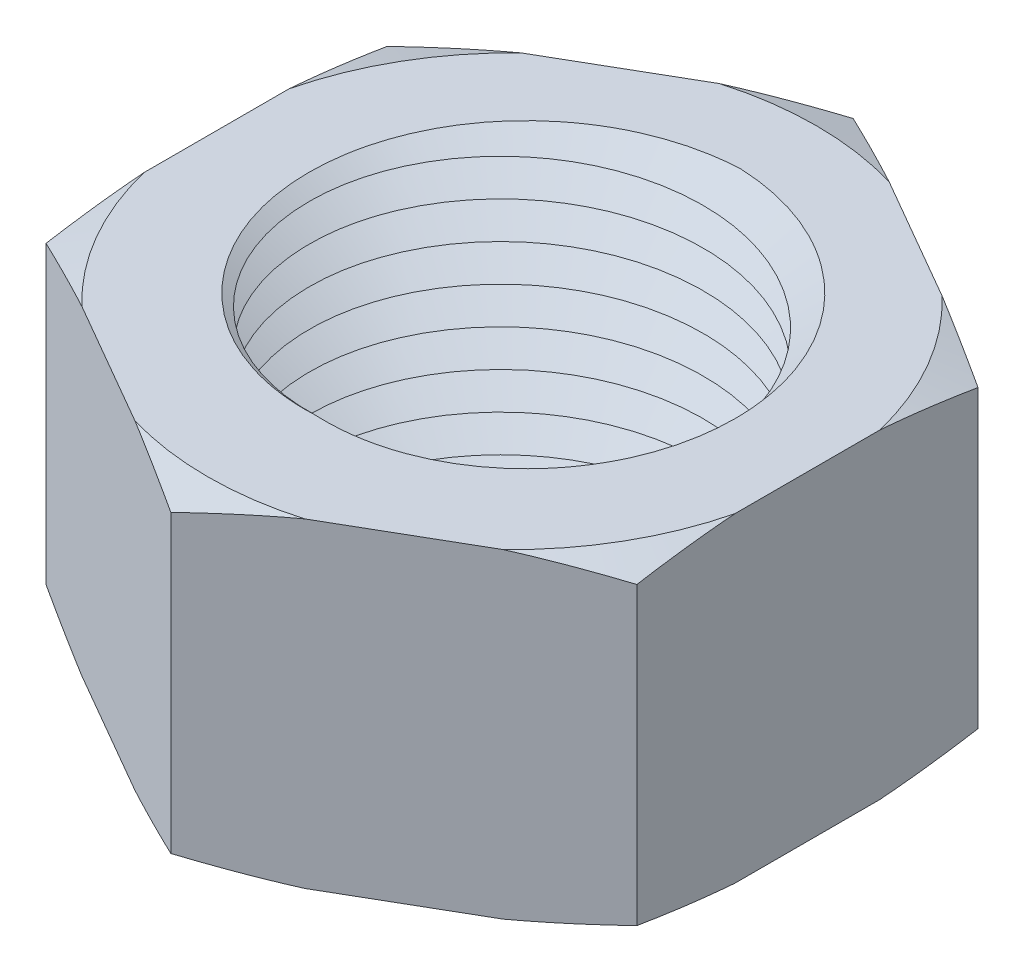
SolidWorks part; units mm, degrees
ref_plane "前视基准面" through (0, 0, 0) normal (0, 0, 1) x (1, 0, 0)
ref_plane "上视基准面" through (0, 0, 0) normal (0, 1, 0) x (1, 0, 0)
ref_plane "右视基准面" through (0, 0, 0) normal (1, 0, 0) x (0, 0, -1)
sketch "草图1" plane through (0, 0, 0) normal (0, 1, 0) x (1, 0, 0)
  line L1 (0, 13.8564) -> (-12, 6.9282)
  line L2 (-12, 6.9282) -> (-12, -6.9282)
  line L3 (-12, -6.9282) -> (0, -13.8564)
  line L4 (0, -13.8564) -> (12, -6.9282)
  line L5 (12, -6.9282) -> (12, 6.9282)
  line L6 (12, 6.9282) -> (0, 13.8564)
  circle A0 centre (0, 0) radius 12 construction
  circle A1 centre (0, 0) radius 8
  dimension "D2" = 16
  dimension "D1" = 24
extrude "凸台-拉伸1" add sketch "草图1" along normal mid plane 13
ref_plane "基准面1" through (0, 0, 0) normal (-0.5, 0, 0.866) x (0.866, 0, 0.5)
sketch "草图2" plane through (0, 0, 0) normal (-0.5, 0, 0.866) x (0.866, 0, 0.5)
  line L0 (12.3564, 6.5) -> (13.8564, 6.5)
  line L1 (6.9282, 6.5) -> (13.8564, 6.5) construction
  line L2 (13.8564, 6.5) -> (13.8564, 6)
  line L3 (13.8564, 6.5) -> (13.8564, -6.5) construction
  line L4 (13.8564, 6) -> (12.3564, 6.5)
  line L5 (0, 0) -> (0, 17.8732) construction
  line L6 (0, 0) -> (20.8438, 0) construction
  line L7 (13.8564, -6) -> (12.3564, -6.5)
  line L8 (13.8564, -6.5) -> (13.8564, -6)
  line L9 (12.3564, -6.5) -> (13.8564, -6.5)
  dimension "D1" = 0.5
  dimension "D2" = 1.5
revolve "切除-旋转1" cut sketch "草图2" angle 360 about L5
sketch "草图3" plane through (0, 6.5, 0) normal (0, 1, 0) x (1, 0, 0)
  circle A0 centre (0, 0) radius 8 construction
  circle A1 centre (0, 0) radius 8
curve "螺旋线/涡状线1" pitch 1.5 height 13 radius 8 centre (0, 6.5, 0) axis (0, -1, 0) start towards (0, 0, -1)
sketch "草图5" plane through (0, 0, 0) normal (1, 0, 0) x (0, 0, -1)
  line L0 (8, 7.2505) -> (8, 5.7495)
  line L1 (8, 5.7495) -> (9.2999, 6.5)
  line L2 (9.2999, 6.5) -> (8, 7.2505)
  point P5 (8, 6.5)
  dimension "D1" = 60
  dimension "D3" = 1.501
sweep "切除-扫描5" cut profiles "草图5" path "螺旋线/涡状线1" align with end faces yes
